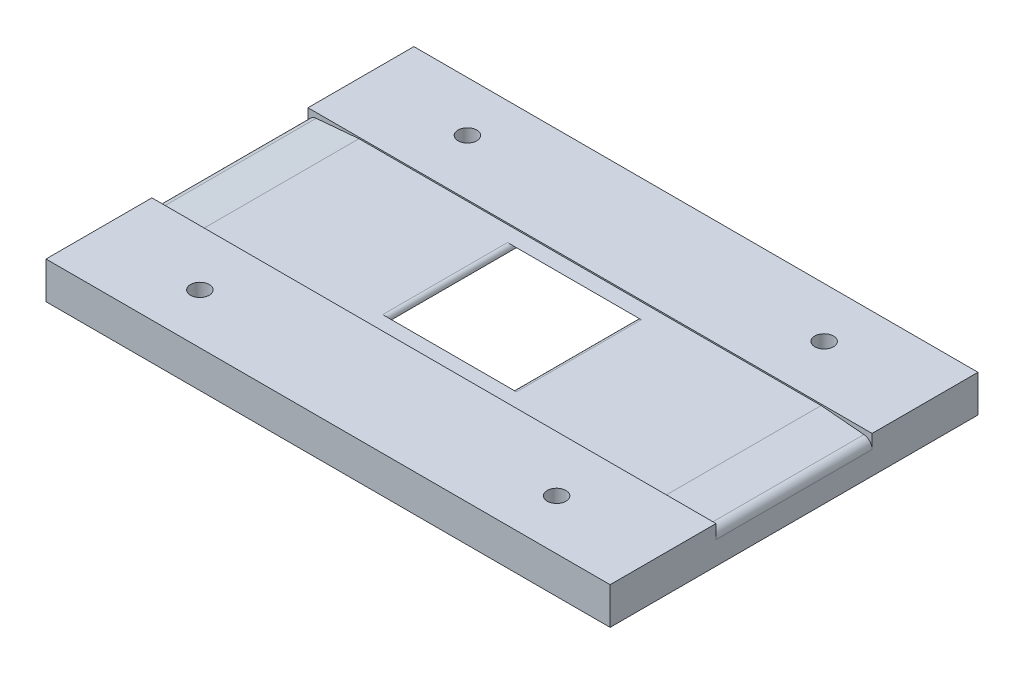
SolidWorks part; units mm, degrees
ref_plane "Спереди" through (0, 0, 0) normal (0, 0, 1) x (1, 0, 0)
ref_plane "Сверху" through (0, 0, 0) normal (0, 1, 0) x (1, 0, 0)
ref_plane "Справа" through (0, 0, 0) normal (1, 0, 0) x (0, 0, -1)
sketch "Эскиз1" plane through (0, 0, 0) normal (0, 1, 0) x (1, 0, 0)
  line L0 (-63.25, 41.25) -> (63.25, 41.25)
  line L1 (-63.25, -41.25) -> (63.25, -41.25)
  line L2 (14, 14) -> (-14, 14)
  line L4 (-63.25, -41.25) -> (-63.25, 41.25)
  line L5 (63.25, 41.25) -> (63.25, -41.25)
  line L6 (-14, 14) -> (-14, -14)
  line L7 (-14, -14) -> (14, -14)
  line L8 (14, -14) -> (14, 14)
extrude "Бобышка-Вытянуть1" add sketch "Эскиз1" along normal blind 8
ref_plane "Плоскость1" through (0, 8, 0) normal (0, 1, 0) x (1, 0, 0)
sketch "Эскиз2" plane through (0, 8, 0) normal (0, 1, 0) x (1, 0, 0)
  line L0 (-63.25, 17.5) -> (63.25, 17.5)
  line L2 (-63.25, 41.25) -> (-63.25, -41.25) construction
  line L3 (-63.25, 17.5) -> (-63.25, 41.25)
  line L4 (-63.25, 41.25) -> (63.25, 41.25)
  line L5 (63.25, 41.25) -> (63.25, 17.5)
  line L6 (63.25, -41.25) -> (63.25, 41.25) construction
  line L8 (-63.25, -17.5) -> (63.25, -17.5)
  line L9 (-63.25, -17.5) -> (-63.25, -41.25)
  line L10 (-63.25, -41.25) -> (63.25, -41.25)
  line L11 (63.25, -41.25) -> (63.25, -17.5)
extrude "Бобышка-Вытянуть2" add sketch "Эскиз2" along normal blind 0.3
chamfer "Фаска1" distance 1 angle 85 2 edges at (63.25, 8, 0) (-63.25, 8, 0) first distance on face at (63.25, 6.15, 0) first distance on face at (-63.25, 6.15, 0)
fillet "Скругление1" radius 2 2 edges at (63.25, 7, 0) (-63.25, 7, 0)
fillet "Скругление2" radius 1 2 edges at (14, 8, 0) (-14, 8, 0)
sketch "Эскиз3" plane through (0, 8, 0) normal (0, 1, 0) x (1, 0, 0)
  circle A0 centre (-40, 30) radius 2.1
  circle A1 centre (40, 30) radius 2.1
  circle A2 centre (-40, -30) radius 2.1
  circle A3 centre (40, -30) radius 2.1
extrude "Вырез-Вытянуть1" cut sketch "Эскиз3" against normal through all both and the other way through all
chamfer "Фаска2" distance 7 angle 50 2 edges at (14, 0, 0) (-14, 0, 0) first distance on face at (14, 3.5, 0) first distance on face at (-14, 3.5, 0)
chamfer "Фаска3" distance 8 angle 50 2 edges at (0, 0, 14) (0, 0, -14) first distance on face at (0, 5.069, 14) first distance on face at (0, 5.069, -14)
